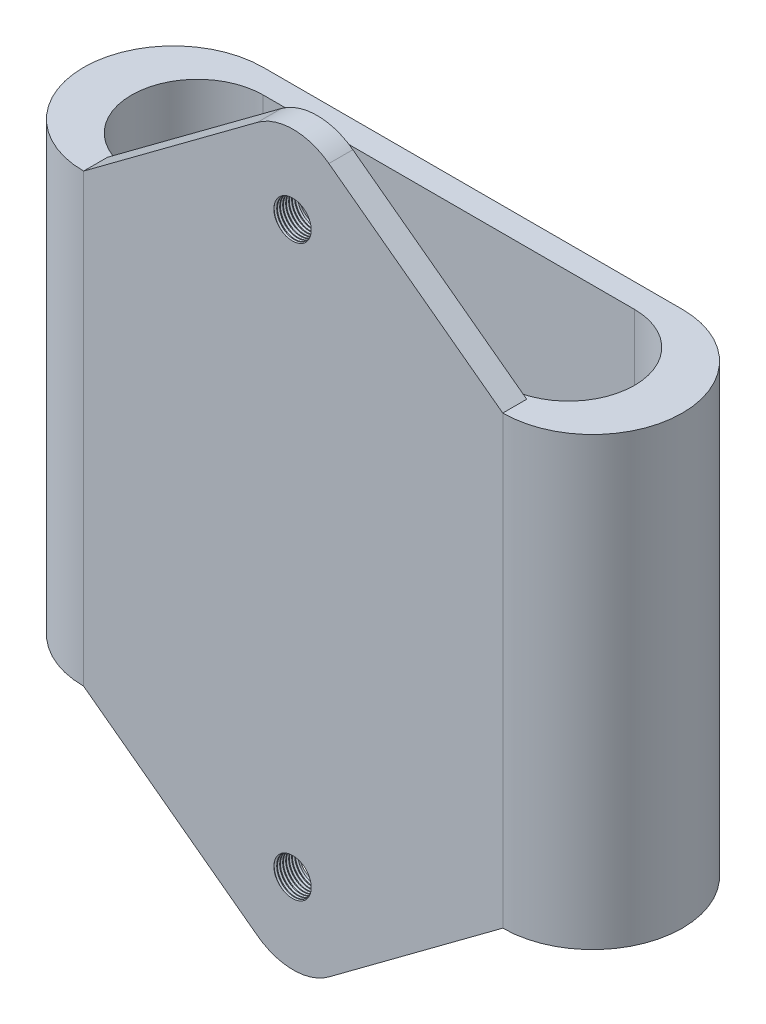
SolidWorks part; units mm, degrees
ref_plane "Front Plane" through (0, 0, 0) normal (0, 0, 1) x (1, 0, 0)
ref_plane "Top Plane" through (0, 0, 0) normal (0, 1, 0) x (1, 0, 0)
ref_plane "Right Plane" through (0, 0, 0) normal (1, 0, 0) x (0, 0, -1)
sketch "Sketch2" plane through (0, 0, 0) normal (0, 1, 0) x (1, 0, 0)
  line L0 (-17.5, 0) -> (17.5, 0) construction
  line L1 (-17.5, 7.5) -> (17.5, 7.5)
  line L2 (-17.5, -7.5) -> (17.5, -7.5)
  line L3 (15.5, 0) -> (-15.5, 0) construction
  line L4 (15.5, -5.5) -> (-15.5, -5.5)
  line L5 (15.5, 5.5) -> (-15.5, 5.5)
  arc A0 (-17.5, 7.5) -> (-17.5, -7.5) centre (-17.5, 0) ccw
  arc A1 (17.5, -7.5) -> (17.5, 7.5) centre (17.5, 0) ccw
  arc A2 (15.5, -5.5) -> (15.5, 5.5) centre (15.5, 0) ccw
  arc A3 (-15.5, 5.5) -> (-15.5, -5.5) centre (-15.5, 0) ccw
  point P2 (0, 0)
  point P8 (-25, 0)
  point P9 (25, 0)
  point P12 (0, 0)
  point P17 (-21, 0)
  point P18 (21, 0)
  dimension "D1" = 50
  dimension "D2" = 15
  dimension "D3" = 42
  dimension "D4" = 2
extrude "Boss-Extrude2" add sketch "Sketch2" along normal blind 37.25
ref_plane "Plane1" through (0, 0, 7.5) normal (0, 0, 1) x (1, 0, 0)
sketch "Sketch3" plane through (0, 0, 7.5) normal (0, 0, 1) x (1, 0, 0)
  line L0 (-17.5, 37.25) -> (-2.9816, 48.0351)
  line L1 (2.9816, 48.0351) -> (17.5, 37.25)
  line L2 (-17.5, 37.25) -> (17.5, 37.25)
  line L3 (17.5, 0) -> (2.9816, -10.7851)
  line L4 (-17.5, 37.25) -> (17.5, 37.25) construction
  line L5 (-17.5, 0) -> (17.5, 0) construction
  line L6 (-2.9816, -10.7851) -> (-17.5, 0)
  line L7 (-17.5, 0) -> (17.5, 0)
  arc A0 (-2.9816, 48.0351) -> (2.9816, 48.0351) centre (0, 44.0214) cw
  arc A1 (-2.9816, -10.7851) -> (2.9816, -10.7851) centre (0, -6.7714) ccw
  point P16 (0, 50.25)
  point P19 (0, -13)
  dimension "D3" = 5
  dimension "D1" = 13
  dimension "D2" = 13
extrude "Boss-Extrude3" add sketch "Sketch3" against normal blind 2
sketch "Sketch5" plane through (0, 0, 5.5) normal (0, 0, -1) x (-1, 0, 0)
  circle A0 centre (0, 42.5214) radius 1.5
  circle A1 centre (0, -5.0214) radius 1.5
  arc A2 (2.9816, 48.0351) -> (-2.9816, 48.0351) centre (0, 44.0214) ccw construction
  arc A3 (-2.9816, -10.7851) -> (2.9816, -10.7851) centre (0, -6.7714) ccw construction
  point P8 (0, 49.0214)
  point P12 (0, -11.7714)
  dimension "D1" = 3
  dimension "D2" = 3
  dimension "D3" = 6.5
  dimension "D4" = 6.75
extrude "Cut-Extrude1" cut sketch "Sketch5" against normal blind 2
thread "Thread1" pitch 0.25 method cut profile "Thread Profile1" start angle 0, offset 0, length 2, pitch 0.25, diameter 3
ref_plane "Plane2" through (1.5, 42.5214, 5.5) normal (0, -1, 0) x (1, 0, 0)
sketch "Thread Profile1" plane through (1.5, 42.5214, 5.5) normal (0, -1, 0) x (1, 0, 0)
  line L0 (0, 0) -> (0, 0.25) construction
  line L1 (0, 0) -> (0.1353, 0.0781)
  line L2 (0.1353, 0.0781) -> (0.1353, 0.1094)
  line L3 (0.1353, 0.1094) -> (0, 0.1875)
  line L4 (0.1353, 0.0937) -> (0, 0.0937) construction
  line L11 (0, 0) -> (0, 0.1875)
  point P2 (0, 0)
  dimension "Pitch" = 0.25
  dimension "Profile_Angle" = 60
  dimension "Profile_Land" = 0.0312
  dimension "Profile_Height" = 0.1353
thread "Thread2" pitch 0.25 method cut profile "Thread Profile2" start angle 0, offset 0, length 2, pitch 0.25, diameter 3
ref_plane "Plane3" through (1.5, -5.0214, 5.5) normal (0, -1, 0) x (1, 0, 0)
sketch "Thread Profile2" plane through (1.5, -5.0214, 5.5) normal (0, -1, 0) x (1, 0, 0)
  line L0 (0, 0) -> (0, 0.25) construction
  line L1 (0, 0) -> (0.1353, 0.0781)
  line L2 (0.1353, 0.0781) -> (0.1353, 0.1094)
  line L3 (0.1353, 0.1094) -> (0, 0.1875)
  line L4 (0.1353, 0.0937) -> (0, 0.0937) construction
  line L11 (0, 0) -> (0, 0.1875)
  point P2 (0, 0)
  dimension "Pitch" = 0.25
  dimension "Profile_Angle" = 60
  dimension "Profile_Land" = 0.0312
  dimension "Profile_Height" = 0.1353
